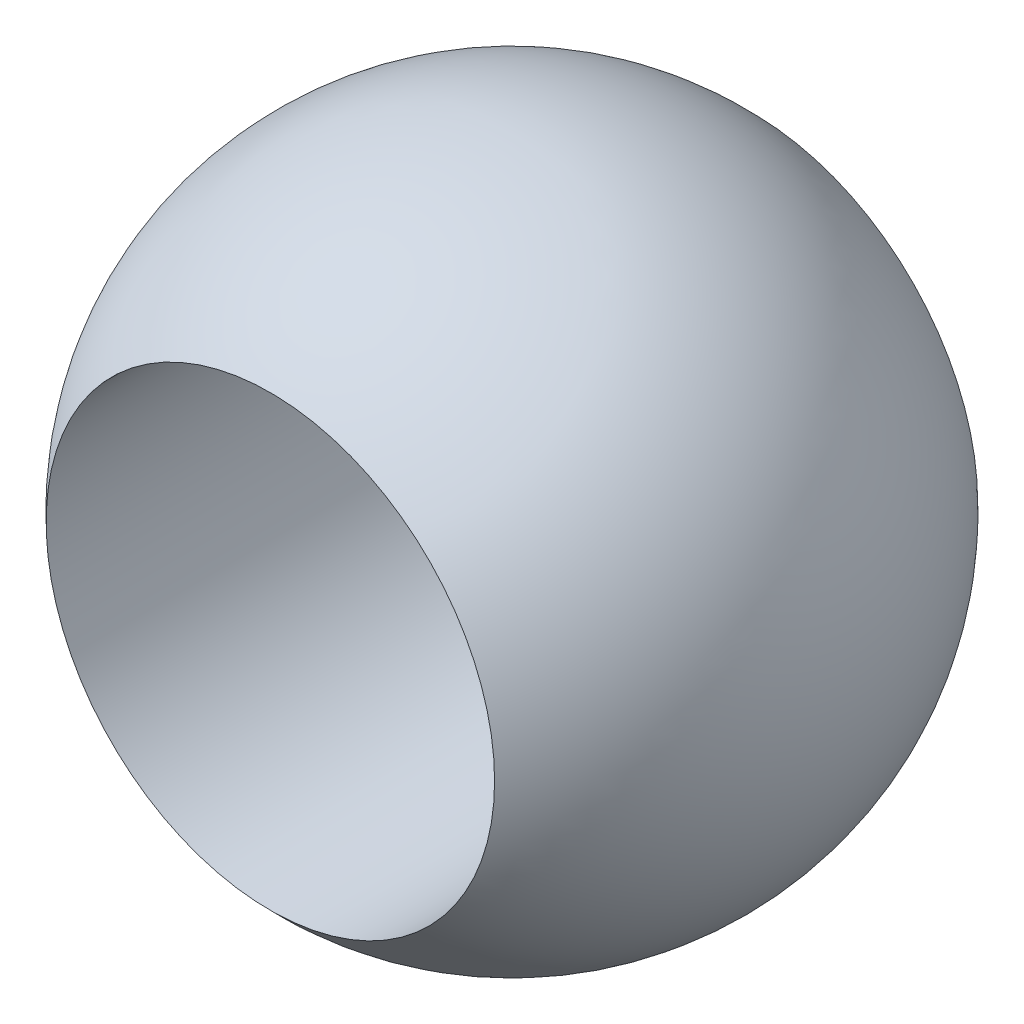
SolidWorks part; units mm, degrees
ref_plane "Front Plane" through (0, 0, 0) normal (0, 0, 1) x (1, 0, 0)
ref_plane "Top Plane" through (0, 0, 0) normal (0, 1, 0) x (1, 0, 0)
ref_plane "Right Plane" through (0, 0, 0) normal (1, 0, 0) x (0, 0, -1)
sketch "Sketch1" plane through (0, 0, 0) normal (0, 1, 0) x (1, 0, 0)
  line L0 (0, -55) -> (0, 55) construction
  line L1 (0, 7) -> (0, -7)
  arc A0 (0, 7) -> (0, -7) centre (0, 0) ccw
  dimension "D1" = 14
revolve "Revolve1" add sketch "Sketch1" angle 360 about L1
sketch "Sketch2" plane through (0, 0, 0) normal (0, 0, 1) x (1, 0, 0)
  circle A0 centre (0, 0) radius 4.7625
extrude "Cut-Extrude1" cut sketch "Sketch2" against normal through all and the other way through all
